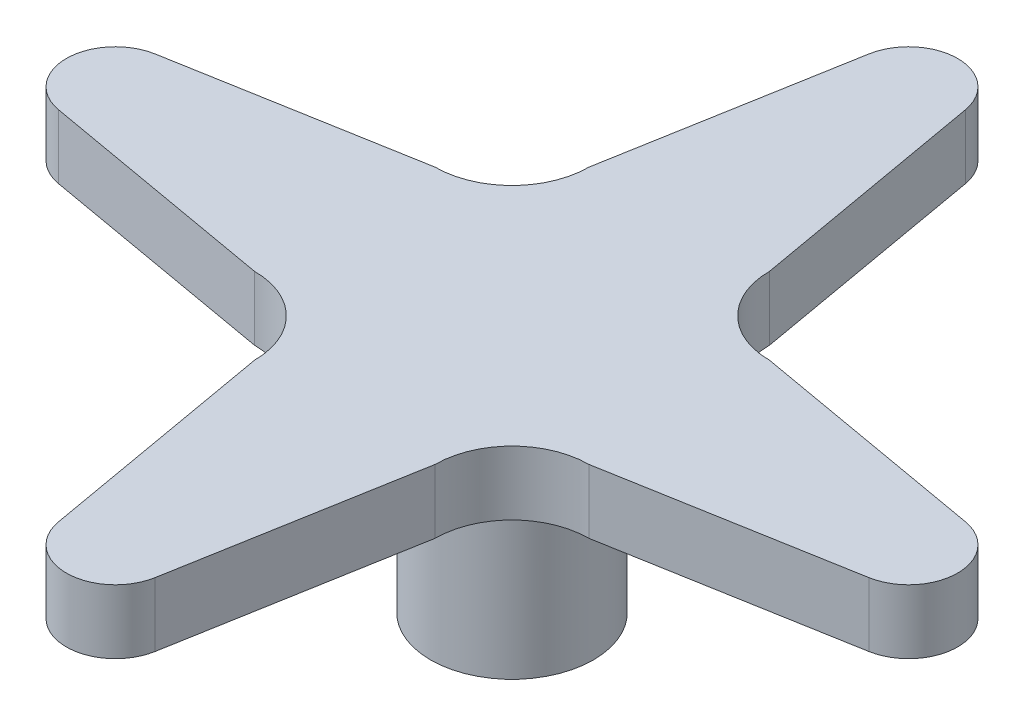
SolidWorks part; units mm, degrees
ref_plane "Front Plane" through (0, 0, 0) normal (0, 0, 1) x (1, 0, 0)
ref_plane "Top Plane" through (0, 0, 0) normal (0, 1, 0) x (1, 0, 0)
ref_plane "Right Plane" through (0, 0, 0) normal (1, 0, 0) x (0, 0, -1)
sketch "Sketch2" plane through (0, 0, 0) normal (0, 1, 0) x (1, 0, 0)
  line L0 (0, 0) -> (0, 50000) construction
  line L1 (2, 16.7718) -> (3.7365, 6.9237)
  line L2 (0, 0) -> (15.933, 15.933) construction
  line L3 (0, -55) -> (0, 55) construction
  line L4 (-12.8998, 18.45) -> (12.8998, 18.45) construction
  line L5 (-55, 0) -> (55, 0) construction
  line L6 (1.1393, 8.2007) -> (8.2007, 1.1393) construction
  line L7 (-2, 16.7718) -> (-3.7365, 6.9237)
  line L8 (16.7718, -2) -> (6.9237, -3.7365)
  line L9 (16.7718, 2) -> (6.9237, 3.7365)
  line L10 (-2, -16.7718) -> (-3.7365, -6.9237)
  line L11 (2, -16.7718) -> (3.7365, -6.9237)
  line L12 (-16.7718, 2) -> (-6.9237, 3.7365)
  line L13 (-16.7718, -2) -> (-6.9237, -3.7365)
  arc A1 (2, 16.7718) -> (-2, 16.7718) centre (0, 16.4191) ccw
  arc A2 (3.7365, 6.9237) -> (4.67, 4.67) centre (6.9237, 6.9237) ccw
  arc A3 (-3.7365, 6.9237) -> (-4.67, 4.67) centre (-6.9237, 6.9237) cw
  arc A4 (16.7718, -2) -> (16.7718, 2) centre (16.4191, 0) ccw
  arc A5 (6.9237, 3.7365) -> (4.67, 4.67) centre (6.9237, 6.9237) cw
  arc A6 (6.9237, -3.7365) -> (4.67, -4.67) centre (6.9237, -6.9237) ccw
  arc A7 (-2, -16.7718) -> (2, -16.7718) centre (0, -16.4191) ccw
  arc A8 (3.7365, -6.9237) -> (4.67, -4.67) centre (6.9237, -6.9237) cw
  arc A9 (-3.7365, -6.9237) -> (-4.67, -4.67) centre (-6.9237, -6.9237) ccw
  arc A10 (-16.7718, 2) -> (-16.7718, -2) centre (-16.4191, 0) ccw
  arc A11 (-6.9237, -3.7365) -> (-4.67, -4.67) centre (-6.9237, -6.9237) cw
  arc A12 (-6.9237, 3.7365) -> (-4.67, 4.67) centre (-6.9237, 6.9237) ccw
  point P12 (0, 18.45)
  point P24 (4.67, 4.67)
  point P55 (0, 0)
  dimension "D4" = 18.45
  dimension "D6" = 4
  dimension "D2" = 10
  dimension "D3" = 10
  dimension "D5" = 2
  dimension "D7" = 45
  dimension "D8" = 90
extrude "Boss-Extrude1" add sketch "Sketch2" along normal mid plane 2.65
ref_plane "Plane1" through (0, 0.325, 0) normal (0, 1, 0) x (1, 0, 0)
sketch "Sketch5" plane through (0, -1.325, 0) normal (0, -1, 0) x (1, 0, 0)
  circle A0 centre (0, 0) radius 3.375
  dimension "D1" = 6.75
extrude "Boss-Extrude4" add sketch "Sketch5" along normal blind 8
sketch "Sketch6" plane through (0, -9.325, 0) normal (0, -1, 0) x (1, 0, 0)
  line L0 (-1.4595, -1.475) -> (1.4595, -1.475)
  circle A0 centre (0, 0) radius 2.075
  point P5 (0, 2.075)
  dimension "D2" = 4.15
  dimension "D1" = 3.55
extrude "Cut-Extrude1" cut sketch "Sketch6" against normal up to surface (8 mm away) contours L0 A0 region at (0, -9.325, 0.1682) up to face at (0, -1.325, 3.375)
